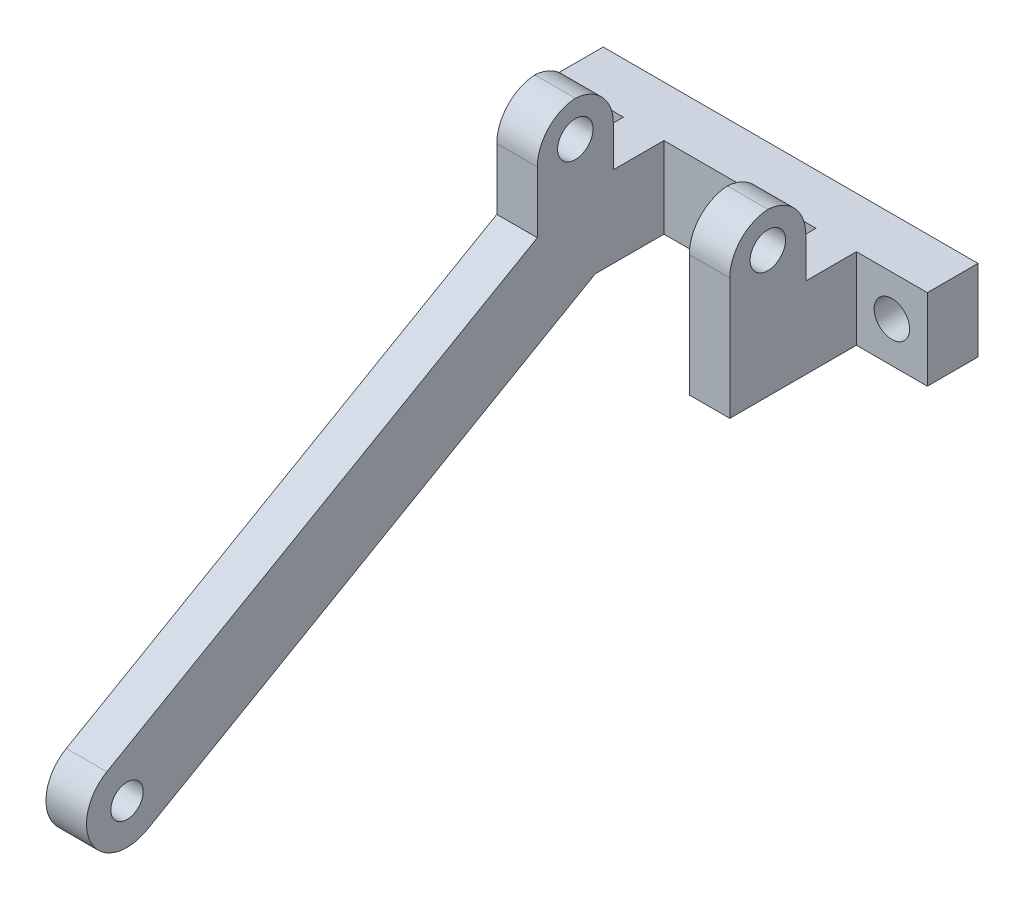
SolidWorks part; units mm, degrees
ref_plane "Front Plane" through (0, 0, 0) normal (0, 0, 1) x (1, 0, 0)
ref_plane "Top Plane" through (0, 0, 0) normal (0, 1, 0) x (1, 0, 0)
ref_plane "Right Plane" through (0, 0, 0) normal (1, 0, 0) x (0, 0, -1)
sketch "Sketch1" plane through (0, 0, 0) normal (0, 0, 1) x (1, 0, 0)
  line L0 (15, 0) -> (-15, 0) construction
  line L1 (-18.5, 4) -> (18.5, 4)
  line L2 (-18.5, 4) -> (-18.5, -4)
  line L3 (-18.5, -4) -> (18.5, -4)
  line L4 (18.5, 4) -> (18.5, -4)
  line L5 (-18.5, 4) -> (18.5, -4) construction
  line L6 (-18.5, -4) -> (18.5, 4) construction
  line L7 (0, -4) -> (0, 4) construction
  circle A0 centre (-15, 0) radius 1.75
  circle A1 centre (15, 0) radius 1.75
  point P0 (0, 0)
  point P12 (0, 0)
  dimension "D3" = 3.5
  dimension "D1" = 37
  dimension "D2" = 8
  dimension "D4" = 15
extrude "Boss-Extrude1" add sketch "Sketch1" along normal blind 5
sketch "Sketch2" plane through (0, 0, 5) normal (0, 0, 1) x (1, 0, 0)
  line L0 (0, 4) -> (0, -4) construction
  line L1 (18.5, 4) -> (-18.5, 4) construction
  line L2 (-18.5, -4) -> (18.5, -4) construction
  line L3 (11.5, -4) -> (7.5, 4) construction
  line L4 (-11.5, 4) -> (-7.5, 4)
  line L5 (-11.5, 4) -> (-11.5, -4)
  line L6 (-11.5, -4) -> (-7.5, -4)
  line L7 (-7.5, 4) -> (-7.5, -4)
  line L8 (-11.5, 4) -> (-7.5, -4) construction
  line L9 (-11.5, -4) -> (-7.5, 4) construction
  line L10 (11.5, 4) -> (7.5, -4) construction
  line L11 (7.5, 4) -> (7.5, -4)
  line L12 (11.5, -4) -> (7.5, -4)
  line L13 (11.5, 4) -> (11.5, -4)
  line L14 (11.5, 4) -> (7.5, 4)
  point P6 (-9.5, 0)
  point P15 (9.5, 0)
  dimension "D1" = 7.5
  dimension "D2" = 4
extrude "Boss-Extrude2" add sketch "Sketch2" along normal blind 12.5
sketch "Sketch4" plane through (0, 4, 0) normal (0, 1, 0) x (1, 0, 0)
  line L0 (-7.5, -17.5) -> (-7.5, -5) construction
  line L1 (-11.5, -17.5) -> (-7.5, -17.5)
  line L2 (-11.5, -17.5) -> (-11.5, -10)
  line L3 (-11.5, -10) -> (-7.5, -10)
  line L4 (-7.5, -17.5) -> (-7.5, -10)
  line L5 (0, 0) -> (0, -5) construction
  line L6 (7.5, -5) -> (-7.5, -5) construction
  line L7 (7.5, -17.5) -> (7.5, -10)
  line L8 (11.5, -10) -> (7.5, -10)
  line L9 (11.5, -17.5) -> (11.5, -10)
  line L10 (11.5, -17.5) -> (7.5, -17.5)
  dimension "D1" = 7.5
extrude "Boss-Extrude3" add sketch "Sketch4" along normal blind 8
sketch "Sketch3" plane through (-11.5, 0, 0) normal (-1, 0, 0) x (0, 0, 1)
  line L0 (10, 8.5) -> (17.5, 8.5) construction
  line L4 (10, 12) -> (10, 4) construction
  line L5 (17.5, 12) -> (17.5, -4) construction
  line L6 (13.75, 8.5) -> (13.75, 12) construction
  line L7 (10, 12) -> (17.5, 12) construction
  circle A0 centre (13.75, 8.5) radius 1.75
  dimension "D1" = 3.5
  dimension "D2" = 8.5
extrude "Cut-Extrude1" cut sketch "Sketch3" against normal through all
fillet "Fillet1" radius 4 4 edges at (-9.5, 12, 10) (9.5, 12, 10) (9.5, 12, 17.5) (-9.5, 12, 17.5)
sketch "Sketch5" plane through (-7.5, 0, 0) normal (1, 0, 0) x (0, 0, -1)
  line L0 (-10, 8) -> (-10, 4) construction
  line L1 (-10, 6.5) -> (-13, 6.5)
  line L2 (-10, 6.5) -> (-10, 1.5)
  line L3 (-10, 1.5) -> (-13, 1.5)
  line L4 (-13, 6.5) -> (-13, 1.5)
  line L5 (-10, 4) -> (-5, 4) construction
  dimension "D1" = 3
  dimension "D2" = 5
  dimension "D3" = 2.5
extrude "Boss-Extrude4" [suppressed] add sketch "Sketch5" along normal up to next
sketch "Sketch6" plane through (-11.5, 0, 0) normal (-1, 0, 0) x (0, 0, 1)
  line L0 (56.0113, -29.4012) -> (11.7824, -4)
  line L1 (17.5, -4) -> (5, -4) construction
  line L2 (11.7824, -4) -> (17.5, 1.9418)
  line L3 (13.75, 8.5) -> (58.0033, -25.9326) construction
  line L4 (17.5, 1.9418) -> (59.9954, -22.4639)
  line L5 (59.9954, -22.4639) -> (56.0113, -29.4012) construction
  line L6 (13.75, 8.5) -> (13.75, -4) construction
  line L7 (17.5, 8) -> (17.5, -4) construction
  circle A0 centre (58.0033, -25.9326) radius 1.6
  arc A1 (56.0113, -29.4012) -> (59.9954, -22.4639) centre (58.0033, -25.9326) ccw
  dimension "D1" = 3.2
  dimension "D2" = 8
  dimension "D3" = 52.114
  dimension "D4" = 56.071
  dimension "D5" = 1.9676
extrude "Boss-Extrude5" add sketch "Sketch6" against normal up to surface (4 mm away) up to face at (-7.5, 6.75, 13.75)
equation "\"X-ROD-SPACING\"=45"
equation "\"Y-ROD-SPACING\"=75"
equation "\"Z-ROD-SPACING\"=17.5"
equation "\"Y-BED-OFFSET\"=2"
equation "\"Y-BED-ROD-INSET\"=3.5"
equation "\"Y-BED-SCREW-SPACING\"=209"
equation "\"Y-BED-SCREW-CUTOUT-SLOT-HEIGHT\"=2"
equation "\"T-SLOT-NUT-FILLET-RADIUS\"=0.25"
equation "\"T-SLOT-SCREW-SHAFT-RADIUS\"=1.75"
equation "\"T-SLOT-SCREW-SHAFT-CUTOUT-LENGTH\"=10.5"
equation "\"T-SLOT-NUT-DEPTH\"=4.2"
equation "\"T-SLOT-NUT-WIDTH\"=3"
equation "\"T-SLOT-NUT-END-DISTANCE\"=8"
equation "\"ACRYLIC-THICKNESS\"=10"
equation "\"ACRYLIC-THICKNESS2\"=4.5"
equation "\"ACRYLIC-TAB-CUTOUT-SIZE\"=\"ACRYLIC-THICKNESS\"+\"ACRYLIC-TAB-TOLERANCE\"*2"
equation "\"ACRYLIC-TAB-TOLERANCE\"=.1"
equation "\"ACRYLIC-TAB-WIDTH\"=\"ACRYLIC-THICKNESS\""
equation "\"ACRYLIC-M3-HOLE\"=3.1"
equation "\"SMOOTHROD-CAP-SCREW-DISTANCE\"=20"
equation "\"FRAME-WIDTH-INNER\"=370"
equation "\"NEMA17-HOLE-SPACING\"=31"
equation "\"NEMA17-CENTRAL-CUTOUT\"=22.5"
equation "\"Z-BRACKET-REACH\"=55"
equation "\"Z-ROD-INSET\"=16"
equation "\"TOP-BRACKET-SPACING\"=40"
equation "\"SMOOTHROD-X-LENGTH\"=350"
equation "\"SMOOTHROD-Y-LENGTH\"=350"
equation "\"SMOOTHROD-Z-LENGTH\"=350"
equation "\"SMOOTHROD-TIGHTENING-HEADROOM\"=.25"
equation "\"LEADSCREW-Z-LENGTH\"=300"
equation "\"SCREW-LENGTH-FRAME\"=\"ACRYLIC-THICKNESS\" + 10"
equation "\"SCREW-LENGTH-MOTOR\"=\"ACRYLIC-THICKNESS\" + 5"
equation "\"SCREW-LENGTH-EXTRUDER\"=28"
equation "\"SCREW-HEAD-RADIUS\"=6"
equation "\"PRINTED-X-SMOOTHROD-DIAMETER\"=8.2"
equation "\"PRINTED-X-SMOOTHROD-CUTOUT\"=10"
equation "\"PRINTED-X-BASE-HEIGHT\"=10"
equation "\"PRINTED-LM8UU-CUTOUT-SIZE\"=15.25"
equation "\"PRINTED-LM8UU-CUTOUT-LENGTH\"=24.5"
equation "\"PRINTED-X-IDLER-HEIGHT\"=16"
equation "\"PSU-MOUNTING-WIDTH\"=95"
equation "\"PSU-MOUNTING-HEIGHT\"=177"
equation "\"Y-BELT-TO-ROD-DISTANCE\"=20"
equation "\"SPOOL-HOLDER-ROD-SPACING\"=150"
equation "\"ACRYLIC-X-CARRIAGE-WIDTH\"=55"
equation "\"ACRYLIC-X-CARRIAGE-HEIGHT\"=75"
equation "\"ACRYLIC-X-CARRIAGE-LM8UU-CUTOUT-WIDTH\"=24.25"
equation "\"ACRYLIC-X-CARRIAGE-LM8UU-CUTOUT-HEIGHT\"=11.5"
equation "\"ACRYLIC-X-CARRIAGE-SCREW-SPACING-X\"=15"
equation "\"ACRYLIC-X-CARRIAGE-SCREW-SPACING-Y\"=33"
equation "\"ACRYLIC-X-CARRIAGE-CENTER-TAB-SPACING\"=14"
equation "\"ACRYLIC-X-CARRIAGE-EXTRUDER-OFFSET\"=26"
equation "\"ACRYLIC-X-CARRIAGE-EXTRUDER-ANGLE\"=90"
equation "\"ACRYLIC-X-CARRIAGE-EXTRUDER-SHELF-DEPTH\"=\"ACRYLIC-X-CARRIAGE-EXTRUDER-OFFSET\" + 28"
equation "\"ACRYLIC-X-CARRIAGE-EXTRUDER-BRACE-SPACING\"=23"
equation "\"ACRYLIC-X-CARRIAGE-EXTRUDER-BRACE-TAB-OFFSET\"=20"
equation "\"ACRYLIC-X-CARRIAGE-EXTRUDER-BRACE-HEIGHT\"=35"
equation "\"ACRYLIC-X-CARRIAGE-EXTRUDER-BRACE-SCREW-SPACING\"=22"
equation "\"ACRYLIC-X-CARRIAGE-DUAL-WIDTH-MULTIPLIER\"=1.65"
equation "\"ACRYLIC-X-CARRIAGE-DUAL-HOTEND-SPACING\"=42"
equation "\"ACRYLIC-X-CARRIAGE-DUAL-WIDTH\"=95"
equation "\"ACRYLIC-X-CARRIAGE-DUAL-HOTEND-SEPARATION\"=35"
equation "\"ACRYLIC-X-CARRIAGE-DUAL-MOUNT-PLATE-DEPTH\"=75"
equation "\"ACRYLIC-X-CARRIAGE-DUAL-MOUNT-BRACE-WIDTH\"=33"
equation "\"ACRYLIC-X-CARRIAGE-DUAL-MOUNT-SCREW-WIDTH\"=40"
equation "\"D3@Sketch1\"=3.5"
equation "\"PRINTED-M3-HOLE\"=3.5"
equation "\"BLOWER-FAN-WIDTH\"=15"
equation "\"D1@Sketch2\"=\"BLOWER-FAN-WIDTH\"/2"
